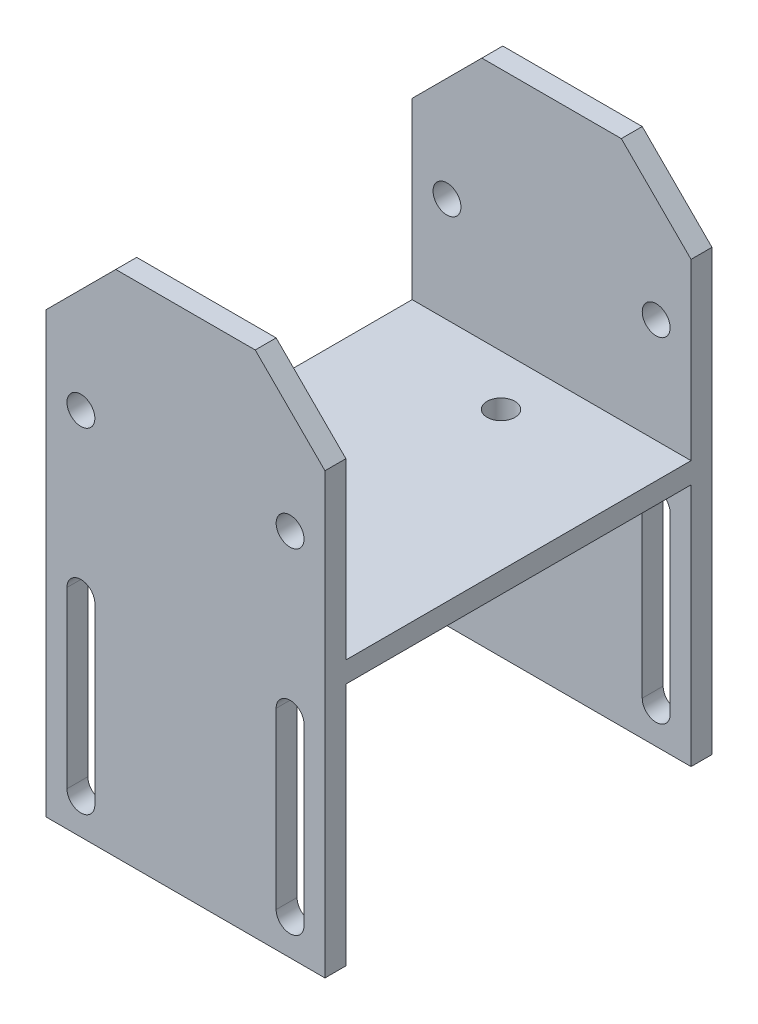
SolidWorks part; units mm, degrees
ref_plane "Alzado" through (0, 0, 0) normal (0, 0, 1) x (1, 0, 0)
ref_plane "Planta" through (0, 0, 0) normal (0, 1, 0) x (1, 0, 0)
ref_plane "Vista lateral" through (0, 0, 0) normal (1, 0, 0) x (0, 0, -1)
sketch "Croquis1" plane through (0, 0, 0) normal (1, 0, 0) x (0, 0, -1)
  line L0 (0, 0) -> (0, 73)
  line L1 (0, 73) -> (3, 73)
  line L2 (3, 73) -> (3, 38)
  line L3 (3, 38) -> (52.5, 38)
  line L4 (52.5, 38) -> (52.5, 73)
  line L5 (52.5, 73) -> (55.5, 73)
  line L6 (55.5, 73) -> (55.5, 0)
  line L7 (55.5, 0) -> (52.5, 0)
  line L8 (52.5, 0) -> (52.5, 35)
  line L9 (52.5, 35) -> (3, 35)
  line L10 (3, 35) -> (3, 0)
  line L11 (3, 0) -> (0, 0)
  point P11 (0, 0)
  dimension "D1" = 3
  dimension "D2" = 55.5
  dimension "D3" = 3
  dimension "D4" = 35
  dimension "D5" = 35
extrude "Saliente-Extruir1" add sketch "Croquis1" along normal blind 40
sketch "Croquis2" plane through (0, 38, 0) normal (0, 1, 0) x (1, 0, 0)
  line L0 (0, 27.75) -> (40, 27.75) construction
  line L1 (0, 52.5) -> (0, 3) construction
  line L2 (40, 52.5) -> (40, 3) construction
sketch "Croquis3" plane through (0, 0, 0) normal (0, 0, 1) x (1, 0, 0)
  line L0 (5, 53) -> (35, 53) construction
  line L1 (40, 73) -> (40, 0) construction
  line L2 (40, 73) -> (0, 73) construction
  line L3 (3, 30) -> (3, 5)
  line L4 (7, 30) -> (7, 5)
  line L5 (3, 17.5) -> (7, 17.5) construction
  line L7 (0, 73) -> (0, 0) construction
  line L8 (40, 0) -> (0, 0) construction
  line L9 (20, 0) -> (20, 73) construction
  line L10 (33, 30) -> (33, 5)
  line L11 (37, 30) -> (37, 5)
  circle A0 centre (5, 53) radius 2
  circle A1 centre (35, 53) radius 2
  arc A4 (3, 30) -> (7, 30) centre (5, 30) cw
  arc A5 (7, 5) -> (3, 5) centre (5, 5) cw
  arc A6 (37, 30) -> (33, 30) centre (35, 30) ccw
  arc A7 (33, 5) -> (37, 5) centre (35, 5) ccw
  point P4 (20, 53)
  point P16 (5, 17.5)
  dimension "D1" = 4
  dimension "D7" = 25
  dimension "D2" = 20
  dimension "D3" = 30
  dimension "D4" = 20
  dimension "D5" = 4
  dimension "D6" = 5
  dimension "D8" = 5
extrude "Cortar-Extruir1" cut sketch "Croquis3" against normal blind 79
chamfer "Chaflán1" distance 10 angle 45 4 edges at (40, 73, -1.5) (40, 73, -54) (0, 73, -54) (0, 73, -1.5)
sketch "Croquis6" plane through (0, 38, 0) normal (0, 1, 0) x (1, 0, 0)
  line L0 (20, 45.25) -> (20, 10.25) construction
  line L3 (20, 10.25) -> (20, 3) construction
  line L4 (30, 3) -> (10, 3) construction
  line L5 (20, 45.25) -> (20, 52.5) construction
  line L6 (30, 52.5) -> (10, 52.5) construction
  circle A0 centre (20, 45.25) radius 2
  circle A1 centre (20, 10.25) radius 2
  dimension "D1" = 4
  dimension "D2" = 35
extrude "Cortar-Extruir2" cut sketch "Croquis6" against normal blind 9
